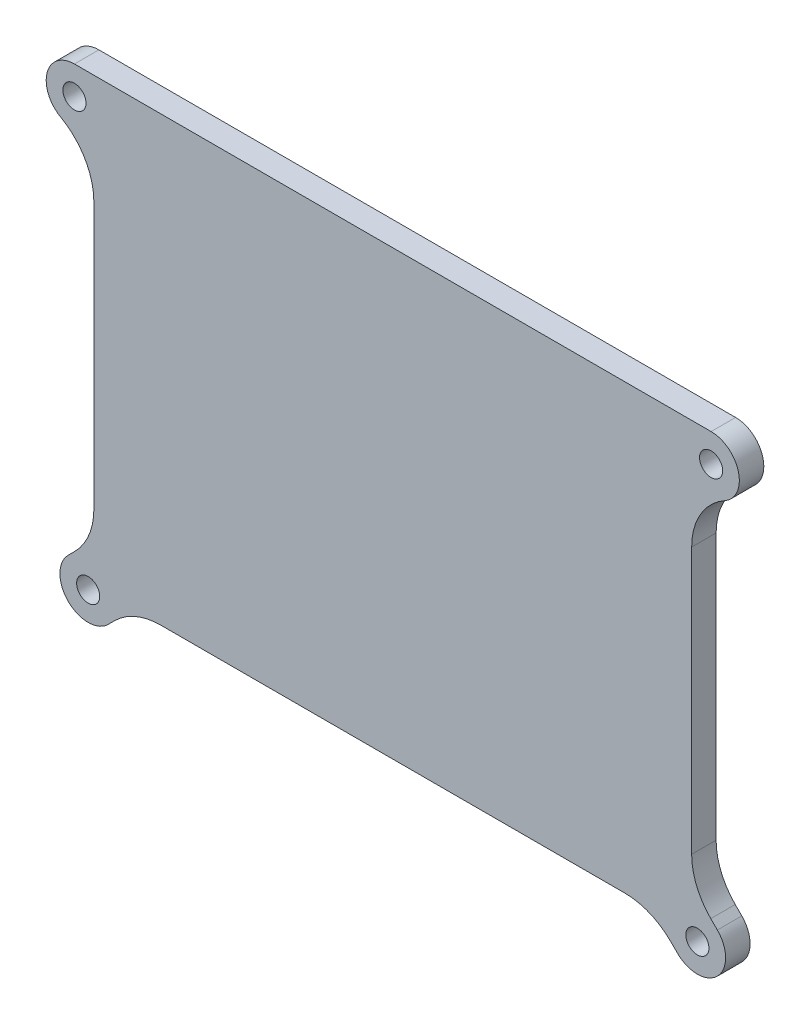
SolidWorks part; units mm, degrees
material "Acrylic (Medium-high impact)"
ref_plane "X-Y Datum" through (0, 0, 0) normal (0, 0, 1) x (1, 0, 0)
ref_plane "X-Z Datum" through (0, 0, 0) normal (0, 1, 0) x (1, 0, 0)
ref_plane "Y-Z Datum" through (0, 0, 0) normal (1, 0, 0) x (0, 0, -1)
sketch "Sketch2" plane through (0, 0, 0) normal (0, 0, 1) x (1, 0, 0)
  line L8 (-58.1812, 21.7343) -> (-58.1812, -30.0613)
  line L9 (-61.901, -39.0416) -> (-63.1828, -40.3234)
  line L10 (-55.4046, -48.1016) -> (-54.1228, -46.8197)
  line L11 (-45.1426, -43.1) -> (45.1426, -43.1)
  line L12 (54.1228, -46.8197) -> (55.4046, -48.1016)
  line L13 (63.1828, -40.3234) -> (61.901, -39.0416)
  line L14 (58.1813, -30.0613) -> (58.1812, 21.7343)
  line L15 (61.9639, 43.1) -> (-61.9639, 43.1)
  line L16 (-58.1812, 21.7343) -> (-58.1812, -30.0613)
  line L17 (-61.901, -39.0416) -> (-63.1828, -40.3234)
  line L18 (-55.4046, -48.1016) -> (-54.1228, -46.8197)
  line L19 (-45.1426, -43.1) -> (45.1426, -43.1)
  line L20 (54.1228, -46.8197) -> (55.4046, -48.1016)
  line L21 (63.1828, -40.3234) -> (61.901, -39.0416)
  line L22 (58.1813, -30.0613) -> (58.1812, 21.7343)
  line L23 (61.9639, 43.1) -> (-61.9639, 43.1)
  arc A10 (-61.9639, 43.1) -> (-64.6587, 32.8054) centre (-61.9639, 37.6) ccw
  arc A11 (-58.1812, 21.7343) -> (-64.6587, 32.8054) centre (-70.8812, 21.7343) ccw
  arc A12 (-61.901, -39.0416) -> (-58.1812, -30.0613) centre (-70.8812, -30.0613) ccw
  arc A13 (-63.1828, -40.3234) -> (-55.4046, -48.1016) centre (-59.2937, -44.2125) ccw
  arc A14 (-45.1426, -43.1) -> (-54.1228, -46.8197) centre (-45.1426, -55.8) ccw
  arc A15 (54.1228, -46.8197) -> (45.1426, -43.1) centre (45.1426, -55.8) ccw
  arc A16 (55.4046, -48.1016) -> (63.1828, -40.3234) centre (59.2937, -44.2125) ccw
  arc A17 (58.1813, -30.0613) -> (61.901, -39.0416) centre (70.8813, -30.0613) ccw
  arc A18 (64.6587, 32.8054) -> (58.1812, 21.7343) centre (70.8812, 21.7343) ccw
  arc A19 (64.6587, 32.8054) -> (61.9639, 43.1) centre (61.9639, 37.6) ccw
  arc A20 (-61.9639, 43.1) -> (-64.6587, 32.8054) centre (-61.9639, 37.6) ccw
  arc A21 (-58.1812, 21.7343) -> (-64.6587, 32.8054) centre (-70.8812, 21.7343) ccw
  arc A22 (-61.901, -39.0416) -> (-58.1812, -30.0613) centre (-70.8812, -30.0613) ccw
  arc A23 (-63.1828, -40.3234) -> (-55.4046, -48.1016) centre (-59.2937, -44.2125) ccw
  arc A24 (-45.1426, -43.1) -> (-54.1228, -46.8197) centre (-45.1426, -55.8) ccw
  arc A25 (54.1228, -46.8197) -> (45.1426, -43.1) centre (45.1426, -55.8) ccw
  arc A26 (55.4046, -48.1016) -> (63.1828, -40.3234) centre (59.2937, -44.2125) ccw
  arc A27 (58.1813, -30.0613) -> (61.901, -39.0416) centre (70.8813, -30.0613) ccw
  arc A28 (64.6587, 32.8054) -> (58.1812, 21.7343) centre (70.8812, 21.7343) ccw
  arc A29 (64.6587, 32.8054) -> (61.9639, 43.1) centre (61.9639, 37.6) ccw
  point P3 (-59.2937, -44.2125)
  point P8 (-61.9639, 37.6)
  point P13 (61.9639, 37.6)
  point P18 (59.2937, -44.2125)
  dimension "D1" = 0
extrude "Boss-Extrude1" add sketch "Sketch2" along normal blind 4.7625
hole_wizard "M4 Clearance Hole1" positions "Sketch9" profile "Sketch10" hole size "M4" standard "ANSI Metric" end condition through all
sketch "Sketch9" plane through (0, 0, 4.7625) normal (0, 0, 1) x (1, 0, 0)
  point P0 (-59.2937, -44.2125)
  point P3 (-61.9639, 37.6)
  point P6 (61.9639, 37.6)
  point P9 (59.2937, -44.2125)
sketch "Sketch10" plane through (-59.2937, -44.2125, 4.7625) normal (1, 0, 0) x (0, -1, 0)
  line L0 (0, 0) -> (0, 4.7625)
  line L1 (0, 4.7625) -> (2.25, 4.7625)
  line L2 (2.25, 4.7625) -> (2.25, 0)
  line L5 (2.25, 0) -> (0, 0)
  line L11 (0, -6.35) -> (0, 107.95) construction
  dimension "Thru Hole Dia." = 4.5
  dimension "Thru Hole Depth" = 4.7625
